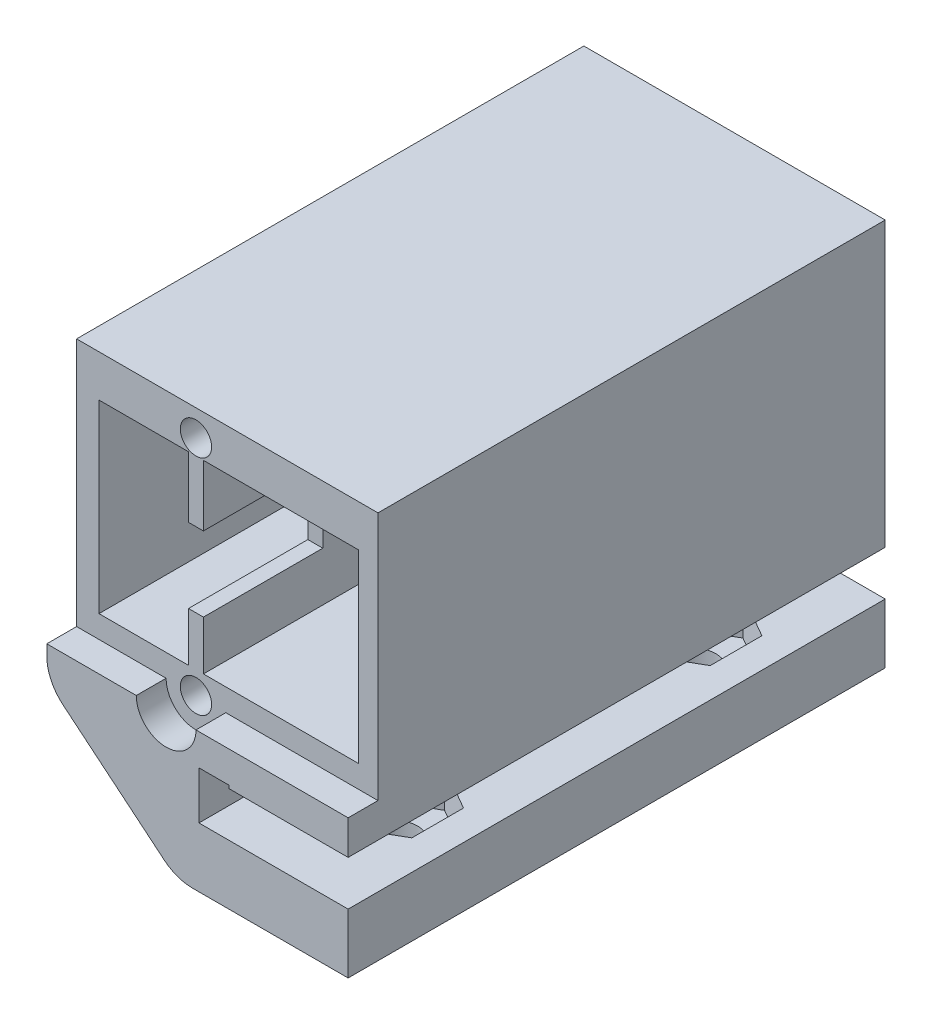
SolidWorks part; units mm, degrees
ref_plane "Plano frontal" through (0, 0, 0) normal (0, 0, 1) x (1, 0, 0)
ref_plane "Plano superior" through (0, 0, 0) normal (0, 1, 0) x (1, 0, 0)
ref_plane "Plano direito" through (0, 0, 0) normal (1, 0, 0) x (0, 0, -1)
sketch "Esboço1" plane through (0, 0, 0) normal (0, 0, 1) x (1, 0, 0)
  line L0 (3.6, 0.4) -> (8.6, 0.4) construction
  line L1 (-10.1, 9.4) -> (10.1, 9.4)
  line L2 (-10.1, 9.4) -> (-10.1, -9.4)
  line L3 (-1.4, -16.6) -> (10.1, -16.6)
  line L4 (10.1, 9.4) -> (10.1, -9.6)
  line L5 (10.1, -9.6) -> (2.1, -9.6)
  line L6 (0.1, -9.4) -> (0.1, -12.6)
  line L7 (0.1, -12.6) -> (10.1, -12.6)
  line L8 (10.1, -12.6) -> (10.1, -16.6)
  line L9 (3.6, 6.4) -> (3.6, -5.6) construction
  line L10 (2.1, -9.6) -> (2.1, -9.4)
  line L11 (2.1, -9.4) -> (0.1, -9.4)
  line L12 (3.6, 6.4) -> (8.6, 6.4) construction
  line L13 (8.6, 6.4) -> (8.6, 0.4) construction
  line L14 (8.6, 9.4) -> (8.6, 6.4) construction
  line L15 (8.6, 6.4) -> (10.1, 6.4) construction
  line L16 (3.6, 6.4) -> (-1.4, 6.4) construction
  line L17 (-1.4, 6.4) -> (-1.4, -5.6) construction
  line L18 (-1.4, -5.6) -> (3.6, -5.6) construction
  line L19 (3.6, -5.6) -> (8.6, -5.6) construction
  line L20 (8.6, -5.6) -> (8.6, 0.4) construction
  line L21 (-1.4, -16.6) -> (-10.1, -9.4)
  line L22 (-10.1, -9.4) -> (-10.1, -16.6) construction
  line L23 (-10.1, -16.6) -> (-1.4, -16.6) construction
  line L25 (-8.6, 6.6) -> (-2.6, 6.6)
  line L26 (-8.6, 6.6) -> (-8.6, -5.8)
  line L27 (-8.6, -5.8) -> (-2.6, -5.8)
  line L28 (-2.6, 6.6) -> (-2.6, -5.8)
  line L29 (-8.6, 6.6) -> (-2.6, -5.8) construction
  line L30 (-8.6, -5.8) -> (-2.6, 6.6) construction
  line L31 (-1.6, 6.6) -> (8.8, 6.6)
  line L32 (-1.6, 6.6) -> (-1.6, -5.8)
  line L33 (-1.6, -5.8) -> (8.8, -5.8)
  line L34 (8.8, 6.6) -> (8.8, -5.8)
  line L35 (-1.6, 6.6) -> (8.8, -5.8) construction
  line L36 (-1.6, -5.8) -> (8.8, 6.6) construction
  circle A0 centre (3.6, 0.4) radius 2.5
  circle A1 centre (3.6, -4.1) radius 1
  circle A2 centre (3.6, 4.9) radius 1
  point P0 (0, 0)
  point P8 (0, 9.4)
  point P9 (11.1254, 0)
  point P18 (-5.6, 0.4)
  point P30 (-10.1, 0)
  point P33 (0, 9.4)
  point P42 (-5.0618, 0.2584)
  point P43 (0.1, -11)
  dimension "D1" = 2
  dimension "D2" = 5
  dimension "D3" = 9
  dimension "D4" = 12
  dimension "D5" = 4
  dimension "D6" = 4
  dimension "D7" = 3
  dimension "D8" = 2
  dimension "D9" = 0.2
  dimension "D10" = 10
  dimension "D11" = 5
  dimension "D12" = 3
  dimension "D14" = 1.5
  dimension "D15" = 1.5
  dimension "D16" = 10.4
  dimension "D17" = 12.4
  dimension "D18" = 6
  dimension "D19" = 1
  dimension "D13" = 1.5
  dimension "D20" = 11.4
extrude "Ressalto-extrusão1" add sketch "Esboço1" along normal mid plane 36 contours L21 L3 L8 L7 L6 L11 L10 L5 L4 L1 L2 L25 L28 L27 L26 L31 L34 L33 L32 | L28 L25 L26 L27 | L34 L31 L32 L33 A2 A1 A0 region at (0, 9.0708, 0) region at (-5.6, 0.4, 0) region at (3.6, 6.4382, 0)
extrude "Corte-extrusão5" cut sketch "Esboço1<3>" against normal offset from surface (34 mm away) 2 from surface contours L28 L25 L26 L27 | L34 L31 L32 L33 A2 A1 A0 region at (-5.6, 0.4, 0) region at (3.6, 6.4382, 0) up to face at (2.1091, -7.9091, -18) starting at face at (2.1091, -7.9091, 18)
sketch "Esboço1<3>" plane through (0, 0, 0) normal (0, 0, 1) x (1, 0, 0) same geometry as "Esboço1"
sketch "Esboço3" plane through (0, 0, 18) normal (0, 0, 1) x (1, 0, 0)
  line L0 (-1.6, 6.6) -> (-1.6, -5.8) construction
  line L1 (-1.6, -2.5) -> (-2.6, -2.5)
  line L2 (-1.6, -2.5) -> (-1.6, 2.5)
  line L3 (-1.6, 2.5) -> (-2.6, 2.5)
  line L4 (-2.6, -2.5) -> (-2.6, 2.5)
  line L5 (-1.6, -2.5) -> (-2.6, 2.5) construction
  line L6 (-1.6, 2.5) -> (-2.6, -2.5) construction
  line L9 (-2.6, -5.8) -> (-2.6, 6.6) construction
  line L10 (-2.6, 6.6) -> (-8.6, 6.6) construction
  line L11 (-8.6, -5.8) -> (-2.6, -5.8) construction
  circle A0 centre (-2.1, 7.65) radius 1.05
  circle A1 centre (-2.1, -7.3) radius 1.05
  point P4 (0, 0)
  point P6 (-2.1, 0)
  point P12 (-5.7423, 0.7463)
  point P14 (-8.1919, 2.5)
  point P15 (-4.8991, 2.5)
  point P16 (-2.4909, 0)
  point P17 (0, 0)
  point P18 (-1.7, 2.5)
  point P19 (0, 0)
  point P20 (-3.3689, 0)
  point P21 (-2.45, -7.5259)
  point P22 (-2.45, 7.2917)
  point P23 (-1.95, 2.5)
  point P24 (-1.6, 2.5)
  point P25 (-2.45, -8.57)
  point P28 (-2.45, 7.1713)
  point P31 (-2.45, 7.25)
  point P34 (-2.6, 2.5)
  point P37 (0, 0)
  point P38 (0, 0)
  dimension "D1" = 2.1
  dimension "D2" = 5
  dimension "D3" = 1.5
  dimension "D4" = 14.95
extrude "Corte-extrusão3" cut sketch "Esboço3" against normal blind 10
sketch "Esboço4" plane through (0, 0, 18) normal (0, 0, 1) x (1, 0, 0)
  line L0 (-10.1, 9.4) -> (-10.1, -7.3)
  line L1 (-10.1, -7.3) -> (-4.1, -7.3)
  line L2 (-0.1, -7.3) -> (10.1, -7.3)
  line L5 (-10.1, 9.4) -> (10.1, 9.4)
  line L6 (10.1, 9.4) -> (10.1, -7.3)
  arc A0 (-4.1, -7.3) -> (-0.1, -7.3) centre (-2.1, -7.3) ccw
  circle A1 centre (-2.1, -7.3) radius 1.05 construction
  point P3 (10.75, -7.7)
  point P7 (-10.1, 9)
  point P9 (10.1, 9)
  dimension "D1" = 2
extrude "Corte-extrusão4" cut sketch "Esboço4" against normal blind 2
sketch "Esboço5" plane through (0, -12.6, 0) normal (0, 1, 0) x (1, 0, 0)
  line L0 (0, 0) -> (15.9501, 0) construction
  line L1 (5.1, 6.5359) -> (8.1, 8.2679)
  line L2 (8.1, 8.2679) -> (8.1, 11.7321)
  line L3 (8.1, 11.7321) -> (5.1, 13.4641)
  line L4 (5.1, 13.4641) -> (2.1, 11.7321)
  line L5 (2.1, 11.7321) -> (2.1, 8.2679)
  line L6 (2.1, 8.2679) -> (5.1, 6.5359)
  line L7 (5.1, -13.4641) -> (8.1, -11.7321)
  line L8 (8.1, -11.7321) -> (8.1, -8.2679)
  line L9 (8.1, -8.2679) -> (5.1, -6.5359)
  line L10 (5.1, -6.5359) -> (2.1, -8.2679)
  line L11 (2.1, -8.2679) -> (2.1, -11.7321)
  line L12 (2.1, -11.7321) -> (5.1, -13.4641)
  line L13 (0.1, -18) -> (10.1, -18) construction
  circle A0 centre (5.1, 10) radius 3 construction
  circle A1 centre (5.1, -10) radius 3 construction
  circle A2 centre (5.1, -10) radius 1.65
  circle A3 centre (5.1, 10) radius 1.65
  point P21 (5.1, -18)
  dimension "D1" = 6
  dimension "D3" = 3.3
  dimension "D2" = 20
extrude "Corte-extrusão6" cut sketch "Esboço5" against normal blind 2.5
extrude "Corte-extrusão7" cut sketch "Esboço5<2>" against normal through all contours A2 | A3
sketch "Esboço5<2>" plane through (0, -12.6, 0) normal (0, 1, 0) x (1, 0, 0) same geometry as "Esboço5"
fillet "Filete1" radius 3 2 edges at (-1.4, -16.6, 0) (-10.1, -9.4, 0)
equation "\"D13@Esboço1\"=\"D15@Esboço1\""
equation "\"D6@Esboço1\"=\"D5@Esboço1\""
